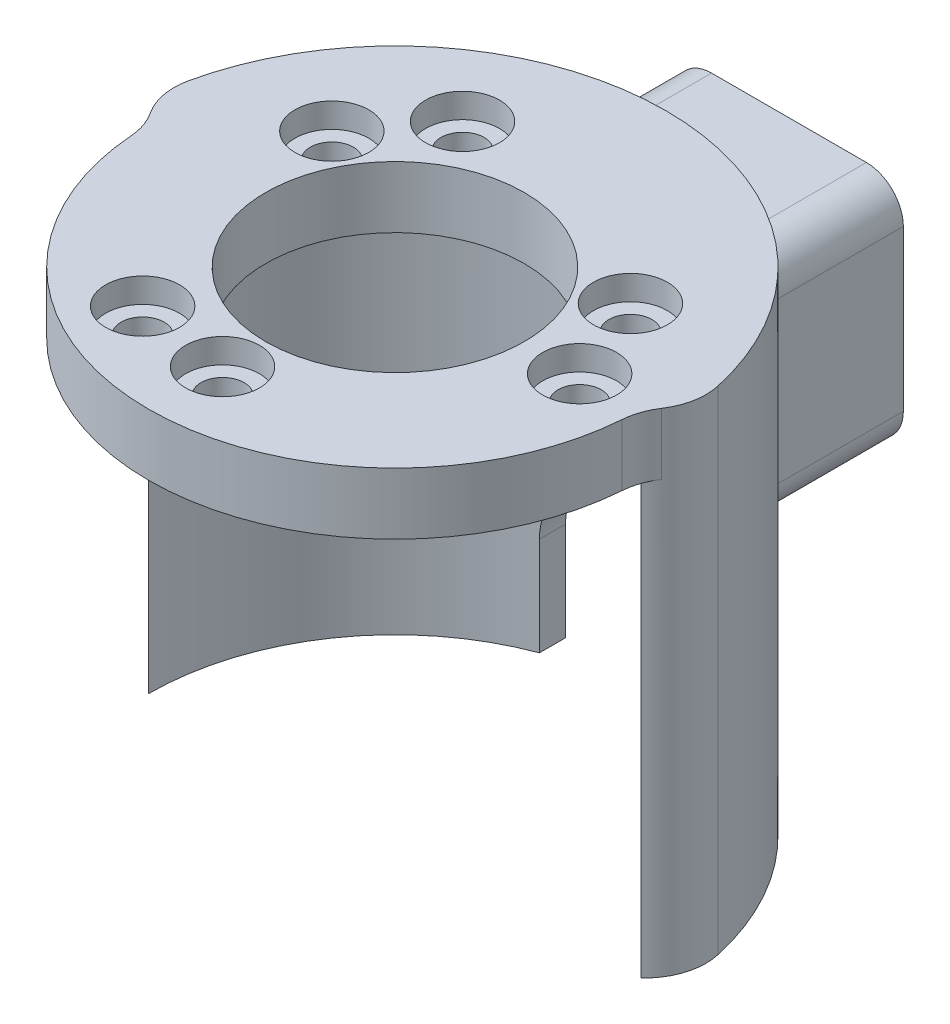
SolidWorks part; units mm, degrees
material "PLA"
ref_plane "Front Plane" through (0, 0, 0) normal (1, 0, 0) x (0, 1, 0)
ref_plane "Top Plane" through (0, 0, 0) normal (0, 0, 1) x (0, 1, 0)
ref_plane "Right Plane" through (0, 0, 0) normal (0, 1, 0) x (-1, 0, 0)
sketch "Sketch1" plane through (0, 0, 0) normal (0, 1, 0) x (-1, 0, 0)
  line L0 (0, 0) -> (0, 14) construction
  line L1 (0, 0) -> (7, 12.1244) construction
  line L2 (-20, 0) -> (-22, 0)
  line L3 (20, 0) -> (22, 0)
  circle A0 centre (0, 0) radius 20
  circle A1 centre (0, 14) radius 1.75
  circle A2 centre (7.5, 12.9904) radius 1.75
  circle A9 centre (0, 0) radius 10.5
  arc A10 (-22, 0) -> (22, 0) centre (0, 0) ccw
  circle A11 centre (12.1244, -7) radius 1.75
  circle A12 centre (7.5, -12.9904) radius 1.75
  circle A13 centre (-12.1244, -7) radius 1.75
  circle A14 centre (-15, 0) radius 1.75
  point P20 (0, 0)
  point P23 (0, 0)
  dimension "D1" = 40
  dimension "D2" = 14
  dimension "D3" = 3.5
  dimension "D6" = 3.5
  dimension "D8" = 21
  dimension "D9" = 22
  dimension "D4" = 15
  dimension "D5" = 30
  dimension "D7" = 3
extrude "Boss-Extrude1" add sketch "Sketch1" along normal blind 5 contours A0 A9 A2 A1 region at (0, 0, 19.4343)
sketch "Sketch2" plane through (0, 5, 0) normal (0, -1, 0) x (1, 0, 0)
  circle A0 centre (0, 14) radius 3
  circle A1 centre (-7.5, 12.9904) radius 3
  circle A8 centre (12.1244, -7) radius 3
  circle A9 centre (15, 0) radius 3
  circle A10 centre (-12.1244, -7) radius 3
  circle A11 centre (-7.5, -12.9904) radius 3
  point P16 (0, 0)
  point P21 (0, 0)
  dimension "D1" = 6
  dimension "D2" = 6
  dimension "D3" = 3
extrude "Cut-Extrude1" cut sketch "Sketch2" along normal blind 2
extrude "Boss-Extrude2" add sketch "Sketch1<3>" along normal up to surface (5 mm away) and the other way blind 35 contours A10 A0 region at (0, 0, -20.4919) up to face at (-12.1244, 5, -10)
sketch "Sketch1<3>" plane through (0, 0, 0) normal (0, 1, 0) x (-1, 0, 0) same geometry as "Sketch1"
fillet "Fillet1" radius 5 1 edges at (22, -15, 0)
fillet "Fillet2" radius 5 1 edges at (20, 2.5, 0)
fillet "Fillet4" radius 5 1 edges at (-22, -15, 0)
fillet "Fillet3" radius 5 1 edges at (-20, 2.5, 0)
ref_plane "Plane2" through (0, 0, -22) normal (0, 0, 1) x (0, 1, 0)
sketch "Sketch4" plane through (0, 0, -22) normal (0, 0, 1) x (0, 1, 0)
  line L0 (-37.1776, 0) -> (-27, 0) construction
  line L1 (-55, 0) -> (55, 0) construction
  line L2 (-37.1776, 7) -> (-27, 7)
  line L3 (-37.1776, -7) -> (-27, -7)
  line L4 (-35, 21.4824) -> (-35, -21.4824) construction
  arc A0 (-37.1776, 7) -> (-37.1776, -7) centre (-37.1776, 0) ccw
  arc A1 (-27, -7) -> (-27, 7) centre (-27, 0) ccw
  point P5 (-32.0888, 0)
  point P10 (-20, 0)
  dimension "D1" = 7
  dimension "D2" = 15
extrude "Cut-Extrude2" cut sketch "Sketch4" along normal through all
sketch "Sketch5" plane through (0, 0, -22) normal (0, 0, 1) x (0, 1, 0)
  line L0 (-55, 0) -> (55, 0) construction
  line L1 (-16.5, 9.2869) -> (-3.5, 9.2869)
  line L2 (-19.5, 6.2869) -> (-19.5, -6.2869)
  line L3 (-16.5, -9.2869) -> (-3.5, -9.2869)
  line L4 (-0.5, 6.2869) -> (-0.5, -6.2869)
  line L5 (5, -21.4824) -> (5, 21.4824) construction
  arc A0 (-19.5, 6.2869) -> (-16.5, 9.2869) centre (-16.5, 6.2869) cw
  arc A1 (-3.5, 9.2869) -> (-0.5, 6.2869) centre (-3.5, 6.2869) cw
  arc A2 (-0.5, -6.2869) -> (-3.5, -9.2869) centre (-3.5, -6.2869) cw
  arc A3 (-16.5, -9.2869) -> (-19.5, -6.2869) centre (-16.5, -6.2869) cw
  point P0 (-7.2378, 0)
  dimension "D1" = 3
  dimension "D2" = 13
  dimension "D3" = 5.5
extrude "Boss-Extrude3" add sketch "Sketch5" along normal up to surface and the other way blind 10 up to face at (-0.0805, -22.1287, -15.5757)
sketch "Sketch6" plane through (0, 0, -32) normal (0, 0, -1) x (1, 0, 0)
  line L0 (0, -55) -> (0, 55) construction
  line L1 (0, 16.9282) -> (-6, 13.4641)
  line L2 (-6, 13.4641) -> (-6, 6.5359)
  line L3 (-6, 6.5359) -> (0, 3.0718)
  line L4 (0, 3.0718) -> (6, 6.5359)
  line L5 (6, 6.5359) -> (6, 13.4641)
  line L6 (6, 13.4641) -> (0, 16.9282)
  line L8 (-21.4824, -5) -> (21.4824, -5) construction
  circle A0 centre (0, 10) radius 6 construction
  dimension "D1" = 15
  dimension "D2" = 12
extrude "Cut-Extrude3" cut sketch "Sketch6" against normal blind 7
sketch "Sketch7" plane through (0, 0, -25) normal (0, 0, -1) x (1, 0, 0)
  line L0 (0, -55) -> (0, 55) construction
  circle A0 centre (0, 10) radius 2.25
extrude "Cut-Extrude4" cut sketch "Sketch7" against normal through all
ref_plane "Plane3" through (0, 0, -17) normal (0, 0, 1) x (0, 1, 0)
sketch "Sketch8" plane through (0, 0, -17) normal (0, 0, 1) x (0, 1, 0)
  circle A0 centre (-10, 0) radius 3.5
extrude "Cut-Extrude5" cut sketch "Sketch8" against normal blind 5
